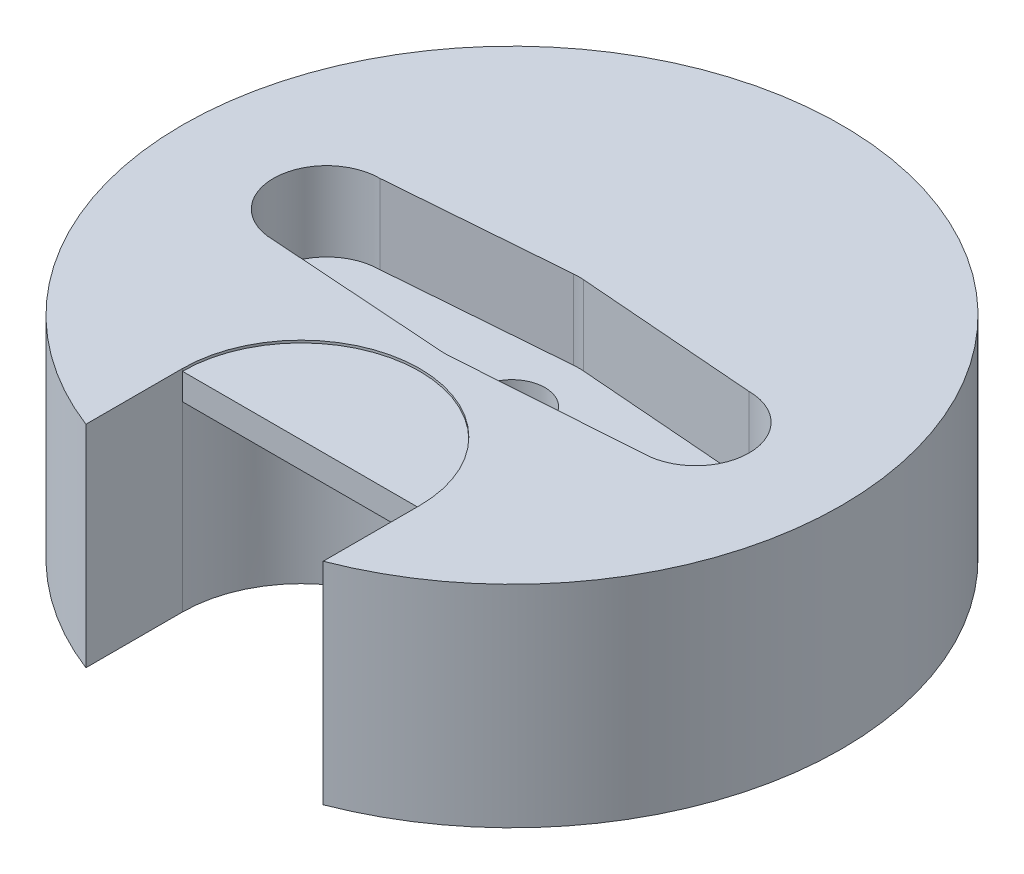
SolidWorks part; units mm, degrees
ref_plane "Ön Düzlem" through (0, 0, 0) normal (0, 0, 1) x (1, 0, 0)
ref_plane "Üst Düzlem" through (0, 0, 0) normal (0, 1, 0) x (1, 0, 0)
ref_plane "Sağ Düzlem" through (0, 0, 0) normal (1, 0, 0) x (0, 0, -1)
sketch "Çizim1" plane through (0, 0, 0) normal (0, 1, 0) x (1, 0, 0)
  line L0 (-4.5, -8) -> (-4.5, -11.6619)
  line L1 (4.5, -8) -> (4.5, -11.6619)
  arc A0 (4.5, -11.6619) -> (-4.5, -11.6619) centre (0, 0) ccw
  arc A1 (4.5, -8) -> (-4.5, -8) centre (0, -8) ccw
  dimension "D1" = 25
  dimension "D2" = 9
extrude "Yükseklik-Ekstrüzyon1" add sketch "Çizim1" along normal blind 5
sketch "Çizim2" plane through (0, 0, 0) normal (0, 1, 0) x (1, 0, 0)
  circle A0 centre (0, 0) radius 2.5
  dimension "D1" = 5
extrude "Kes-Ekstrüzyon3" cut sketch "Çizim2" along normal blind 2.5
sketch "Çizim3" plane through (0, 2.5, 0) normal (0, -1, 0) x (1, 0, 0)
  circle A0 centre (0, 0) radius 1.25
extrude "Kes-Ekstrüzyon4" cut sketch "Çizim3" against normal through all
sketch "Çizim5" plane through (0, 5, 0) normal (0, 1, 0) x (1, 0, 0)
  circle A3 centre (-6.45, -0.0087) radius 0.6
  circle A4 centre (6.45, 0.0087) radius 0.6
extrude "Kes-Ekstrüzyon5" cut sketch "Çizim5" against normal blind 2.5
sketch "Çizim6" plane through (0, 5, 0) normal (0, 1, 0) x (1, 0, 0)
  line L0 (-7, 1.9913) -> (-0.1973, 2.5233)
  line L1 (-7, -2.0518) -> (-0.175, -2.525)
  line L2 (0, -2.75) -> (0, 2.75) construction
  line L3 (7, -2.0518) -> (0.175, -2.525)
  line L4 (7, 1.9913) -> (0.1973, 2.5233)
  line L5 (-4.5, -8) -> (-4.5, -11.6619)
  line L6 (4.5, -8) -> (4.5, -11.6619)
  arc A0 (0.1973, 2.5233) -> (-0.1973, 2.5233) centre (0, 0) ccw
  arc A1 (-7, 1.9913) -> (-7, -2.0518) centre (-7, -0.0303) ccw
  arc A2 (-0.175, -2.525) -> (0.175, -2.525) centre (0, 0) ccw
  arc A3 (7, 1.9913) -> (7, -2.0518) centre (7, -0.0303) cw
  arc A4 (4.5, -11.6619) -> (-4.5, -11.6619) centre (0, 0) ccw
  arc A5 (4.5, -8) -> (-4.5, -8) centre (0, -8) ccw
  arc M4 (-4.5, -8) -> (4.5, -8) centre (0, -8) cw
  line M5 (4.5, -8) -> (4.5, -11.6619)
  arc M6 (4.5, -11.6619) -> (-4.5, -11.6619) centre (0, 0) ccw
  line M7 (-4.5, -11.6619) -> (-4.5, -8)
  dimension "D1" = 7
extrude "Yükseklik-Ekstrüzyon3" add sketch "Çizim6" along normal blind 3 contours L4 A3 L3 A2 L1 A1 L0 A0 M7 M4 M5 M6 region at (-4.8477, 5, 9.831)
sketch "Sketch1" plane through (0, 7.9086, 0) normal (0, -1, 0) x (1, 0, 0)
  line L0 (-4.5, 8) -> (4.5, 8)
  arc A0 (-4.5, 8) -> (4.5, 8) centre (0, 8) ccw construction
  arc A1 (-4.5, 8) -> (4.5, 8) centre (0, 8) ccw
extrude "Boss-Extrude1" add sketch "Sketch1" along normal blind 6
chamfer "Chamfer1" distance 5 angle 45 1 edges at (0, 1.9086, 8)
